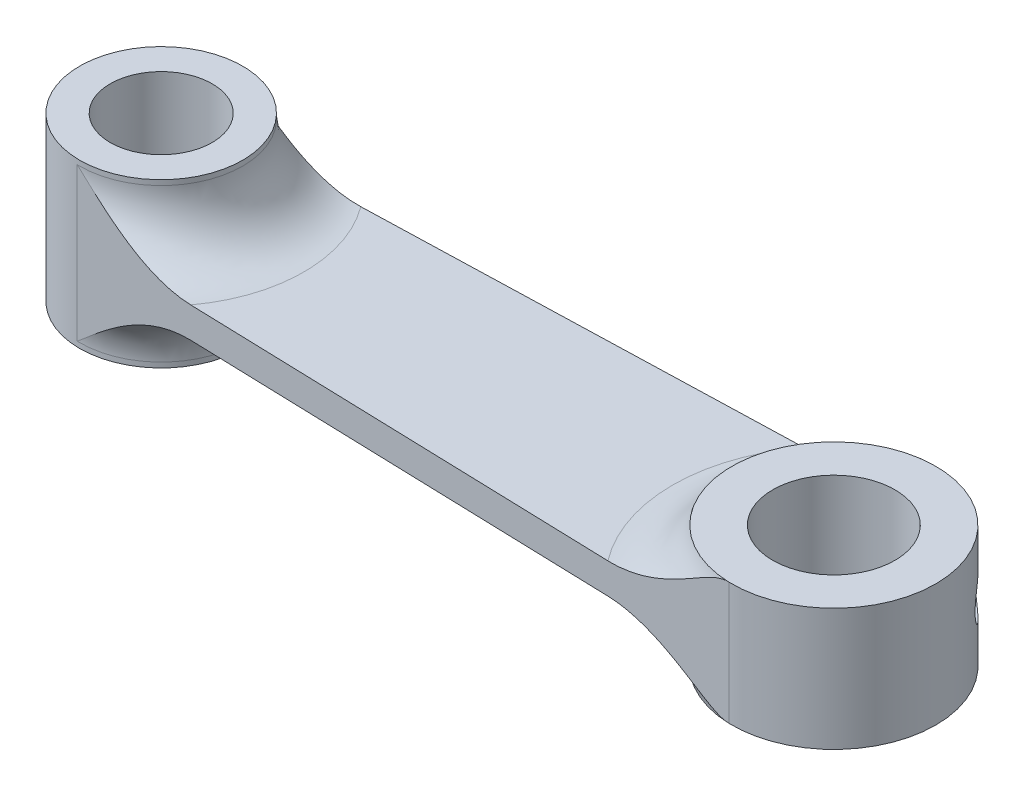
SolidWorks part; units mm, degrees
material "AISI 1035 Steel (SS)"
ref_plane "Front Plane" through (0, 0, 0) normal (0, 0, 1) x (1, 0, 0)
ref_plane "Top Plane" through (0, 0, 0) normal (0, 1, 0) x (1, 0, 0)
ref_plane "Right Plane" through (0, 0, 0) normal (1, 0, 0) x (0, 0, -1)
sketch "Sketch1" plane through (0, 0, 0) normal (0, 1, 0) x (1, 0, 0)
  line L0 (-16.5, 0) -> (16.5, 0) construction
  line L1 (-16.6212, 3.9982) -> (16.3485, 4.9977)
  line L2 (-16.6212, -3.9982) -> (16.3485, -4.9977)
  arc A0 (-16.6212, 3.9982) -> (-16.6212, -3.9982) centre (-16.5, 0) ccw
  arc A1 (16.3485, -4.9977) -> (16.3485, 4.9977) centre (16.5, 0) ccw
  circle A2 centre (-16.5, 0) radius 2.5
  circle A3 centre (16.5, 0) radius 3
  point P3 (0, 0)
  dimension "D2" = 8
  dimension "D3" = 10
  dimension "D4" = 5
  dimension "D5" = 6
  dimension "D1" = 33
extrude "Boss-Extrude1" add sketch "Sketch1" along normal mid plane 1.5
sketch "Sketch2" plane through (0, 0, 0) normal (0, 1, 0) x (1, 0, 0)
  circle A0 centre (-16.5, 0) radius 4
  circle A1 centre (-16.5, 0) radius 2.5 construction
  circle A2 centre (-16.5, 0) radius 2.5
  dimension "D1" = 8
extrude "Boss-Extrude2" add sketch "Sketch2" along normal mid plane 8
sketch "Sketch4" plane through (0, 0, 0) normal (0, 1, 0) x (1, 0, 0)
  circle A0 centre (16.5, 0) radius 5
  circle A1 centre (16.5, 0) radius 3 construction
  circle A2 centre (16.5, 0) radius 3
  dimension "D1" = 10
extrude "Boss-Extrude3" add sketch "Sketch4" along normal mid plane 6
ref_plane "Plane1" through (11.7855, 0, -11.7855) normal (0.7071, 0, -0.7071) x (0, -1, 0)
sketch "Sketch7" plane through (11.7855, 0, -11.7855) normal (0.7071, 0, -0.7071) x (0, -1, 0)
  line L0 (0, 5.5) -> (0, -5.5) construction
  line L2 (3, -6.6673) -> (0.75, -6.6673) construction
  circle A0 centre (0, -11.6673) radius 1
  dimension "D1" = 2
  dimension "D2" = 5
extrude "Cut-Extrude1" cut sketch "Sketch7" against normal blind 4
fillet "Fillet1" radius 3 2 edges at (-12.5, -0.75, 0) (-12.5, 0.75, 0)
fillet "Fillet2" radius 3 2 edges at (11.5, -0.75, 0) (11.5, 0.75, 0)
